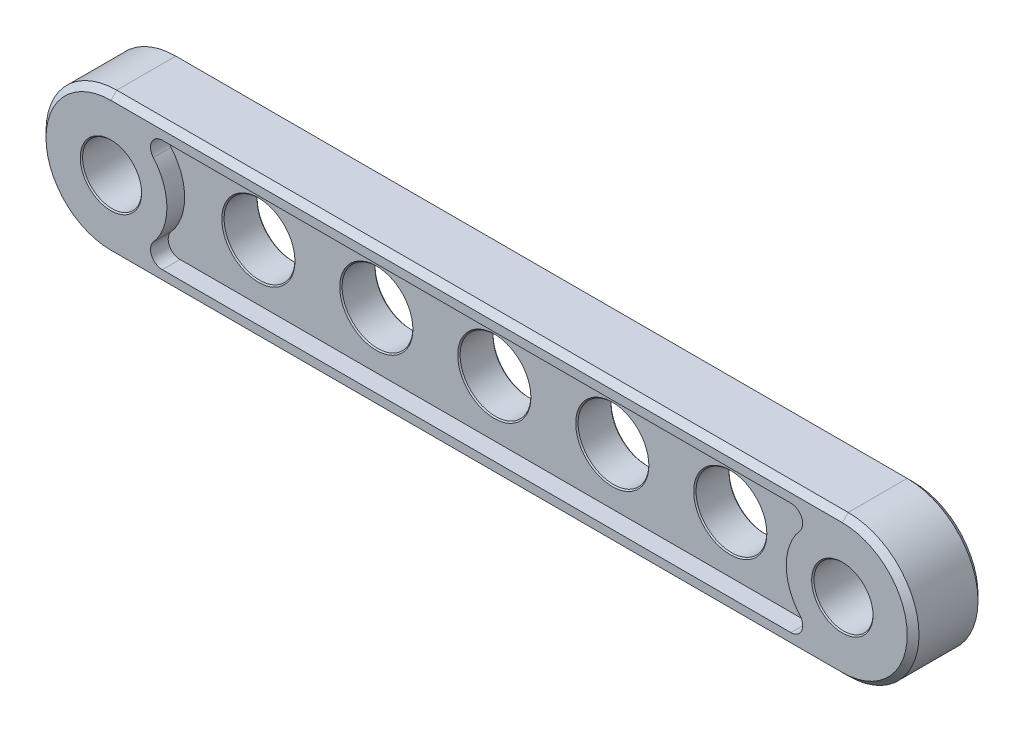
SolidWorks part; units mm, degrees
note: The reader was unsure of these and kept them because the rebuilt part matched: shared geometry of "Sketch1<3>".
ref_plane "Front Plane" through (0, 0, 0) normal (0, 0, 1) x (1, 0, 0)
ref_plane "Top Plane" through (0, 0, 0) normal (0, 1, 0) x (1, 0, 0)
ref_plane "Right Plane" through (0, 0, 0) normal (1, 0, 0) x (0, 0, -1)
sketch "Sketch1" plane through (0, 0, 0) normal (0, 0, 1) x (1, 0, 0)
  line L0 (-31, 0) -> (31, 0) construction
  line L1 (-31, 6) -> (31, 6)
  line L2 (-31, -6) -> (31, -6)
  line L3 (0, 0) -> (3, 0) construction
  line L4 (0, 0) -> (-10, 0) construction
  line L5 (29.5777, 4.5321) -> (31, 4.75) construction
  line L6 (-26.6411, 4.75) -> (26.6411, 4.75)
  line L8 (-26.6411, -4.75) -> (26.6411, -4.75)
  line L10 (-31, 4.75) -> (-29.5777, 4.5321) construction
  line L11 (-31, -4.75) -> (-29.5777, -4.5321) construction
  line L12 (7, 0) -> (10, 0) construction
  line L13 (29.5777, -4.5321) -> (31, -4.75) construction
  arc A0 (-31, 6) -> (-31, -6) centre (-31, 0) ccw
  arc A1 (31, -6) -> (31, 6) centre (31, 0) ccw
  circle A2 centre (-31, 0) radius 2.5
  arc A3 (-27.3992, -3.0978) -> (-27.3992, 3.0978) centre (-31, 0) ccw
  circle A4 centre (31, 0) radius 2.5
  arc A5 (27.3992, 3.0978) -> (27.3992, -3.0978) centre (31, 0) ccw
  circle A6 centre (0, 0) radius 3
  circle A7 centre (10, 0) radius 3
  circle A8 centre (20, 0) radius 3
  circle A9 centre (-10, 0) radius 3
  circle A10 centre (-20, 0) radius 3
  arc A11 (27.3992, 3.0978) -> (26.6411, 4.75) centre (26.6411, 3.75) ccw
  arc A12 (-27.3992, 3.0978) -> (-26.6411, 4.75) centre (-26.6411, 3.75) cw
  arc A13 (-26.6411, -4.75) -> (-27.3992, -3.0978) centre (-26.6411, -3.75) cw
  arc A14 (26.6411, -4.75) -> (27.3992, -3.0978) centre (26.6411, -3.75) ccw
  point P2 (0, 0)
  dimension "D1" = 5
  dimension "D2" = 5
  dimension "D4" = 6
  dimension "D5" = 9.5
  dimension "D6" = 9.5
  dimension "D7" = 6
  dimension "D13" = 1
  dimension "D14" = 1
  dimension "D3" = 62
  dimension "D9" = 10
  dimension "D11" = 10
  dimension "D12" = 9.5
  dimension "D8" = 3
  dimension "D10" = 3
extrude "Boss-Extrude1" add sketch "Sketch1" along normal mid plane 6 contours L2 A1 L1 A0 A14 L8 A13 A3 A12 L6 A11 A5 A4 A2
extrude "Boss-Extrude2" add sketch "Sketch1<3>" along normal mid plane 3 contours L8 A14 A5 A11 L6 A12 A3 A13 A6 A7 A8 A9 A10
sketch "Sketch1<3>" plane through (0, 0, 0) normal (0, 0, 1) x (1, 0, 0) same geometry as "Sketch1"
chamfer "Chamfer1" distance 0.5 angle 45 8 edges at (37, 0, -3) (0, 6, -3) (-37, 0, -3) (0, -6, -3) (-37, 0, 3) (0, 6, 3) (37, 0, 3) (0, -6, 3)
chamfer "Chamfer3" distance 0.1 angle 45 14 edges at (33.5, 0, -3) (33.5, 0, 3) (23, 0, -1.5) (23, 0, 1.5) (13, 0, -1.5) (13, 0, 1.5) (3, 0, -1.5) (3, 0, 1.5) (-7, 0, -1.5) (-7, 0, 1.5) (-28.5, 0, -3) (-28.5, 0, 3) (-17, 0, -1.5) (-17, 0, 1.5)
